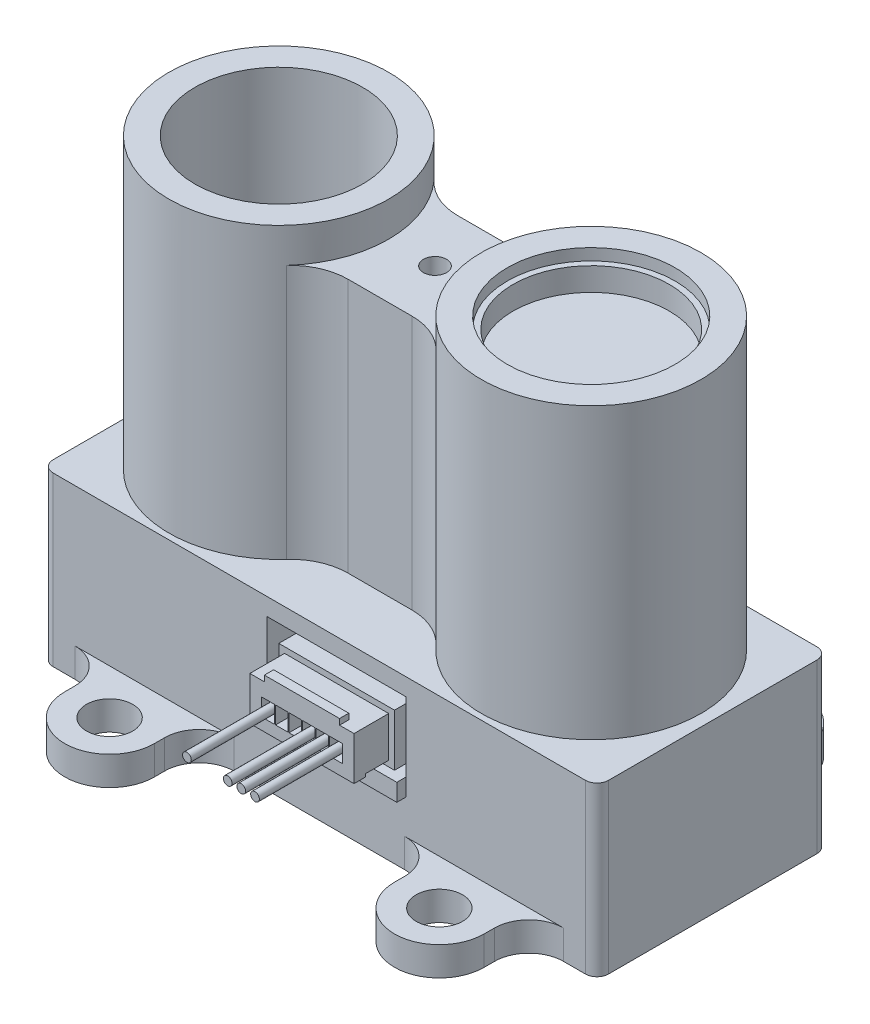
SolidWorks part; units mm, degrees
material "LiDar"
ref_plane "Front Plane" through (0, 0, 0) normal (0, 0, 1) x (1, 0, 0)
ref_plane "Top Plane" through (0, 0, 0) normal (0, 1, 0) x (1, 0, 0)
ref_plane "Right Plane" through (0, 0, 0) normal (1, 0, 0) x (0, 0, -1)
sketch "Sketch1" plane through (0, 0, 0) normal (0, 1, 0) x (1, 0, 0)
  line L1 (-24, 10) -> (24, 10)
  line L2 (-24, 10) -> (-24, -10)
  line L3 (-24, -10) -> (24, -10)
  line L4 (24, 10) -> (24, -10)
  point P4 (0, 10)
  point P6 (-24, 0)
  dimension "D1" = 20
  dimension "D2" = 48
extrude "Boss-Extrude1" add sketch "Sketch1" along normal blind 14.5
fillet "Fillet1" radius 1 4 edges at (-24, 7.25, -10) (-24, 7.25, 10) (24, 7.25, -10) (24, 7.25, 10)
sketch "Sketch2" plane through (0, 14.5, 0) normal (0, 1, 0) x (1, 0, 0)
  line L0 (-24, 9) -> (-24, -9) construction
  line L1 (0, -7.975) -> (0, 7.975) construction
  circle A0 centre (-13.5, 0) radius 9.5
  circle A1 centre (13.5, 0) radius 9.5
  point P2 (-23, 0)
  dimension "D1" = 19
  dimension "D2" = 1
extrude "Boss-Extrude2" add sketch "Sketch2" along normal blind 25
sketch "Sketch3" plane through (0, 14.5, 0) normal (0, 1, 0) x (1, 0, 0)
  line L1 (-5.2728, 4.75) -> (5.2728, 4.75)
  line L2 (-5.2728, 4.75) -> (-5.2728, -4.75)
  line L3 (-5.2728, -4.75) -> (5.2728, -4.75)
  line L4 (5.2728, 4.75) -> (5.2728, -4.75)
  circle A0 centre (-13.5, 0) radius 9.5 construction
  circle A1 centre (13.5, 0) radius 9.5 construction
  point P8 (-5.2728, 0)
  dimension "D1" = 9.5
extrude "Boss-Extrude3" add sketch "Sketch3" along normal blind 22
fillet "Fillet2" radius 5 4 edges at (5.2728, 25.5, -4.75) (-5.2728, 25.5, -4.75) (5.2728, 25.5, 4.75) (-5.2728, 25.5, 4.75)
sketch "Sketch4" plane through (0, 36.5, 0) normal (0, 1, 0) x (1, 0, 0)
  circle A0 centre (0, 0) radius 1
  dimension "D1" = 2
extrude "Cut-Extrude1" cut sketch "Sketch4" against normal blind 5
sketch "Sketch5" plane through (0, 39.5, 0) normal (0, 1, 0) x (1, 0, 0)
  circle A0 centre (-13.5, 0) radius 7.25
  circle A1 centre (-13.5, 0) radius 9.5 construction
  dimension "D1" = 14.5
extrude "Cut-Extrude2" cut sketch "Sketch5" against normal blind 13
sketch "Sketch6" plane through (0, 0, 0) normal (0, 0, 1) x (1, 0, 0)
  line L0 (-20.75, 39.5) -> (-20.75, 26.5) construction
  line L1 (-20.75, 28.5) -> (-20.25, 28.5)
  line L2 (-20.75, 28.5) -> (-20.75, 26.5)
  line L3 (-20.75, 26.5) -> (-20.25, 26.5)
  line L4 (-20.25, 28.5) -> (-20.25, 26.5)
  line L5 (-6.25, 26.5) -> (-20.75, 26.5) construction
  line L6 (-13.5, 39.5) -> (-13.5, 26.5) construction
  line L7 (-6.25, 39.5) -> (-20.75, 39.5) construction
  dimension "D1" = 2
  dimension "D2" = 0.5
revolve "Revolve1" add sketch "Sketch6" angle 360 about L6
sketch "Sketch7" plane through (0, 0, 0) normal (0, 0, 1) x (1, 0, 0)
  line L0 (-20.25, 26.5) -> (-13.5, 26.5)
  line L1 (-6.75, 26.5) -> (-20.25, 26.5) construction
  line L2 (-13.5, 26.5) -> (-13.5, 28.5)
  line L3 (-6.75, 28.5) -> (-20.25, 28.5) construction
  ellipse E0 centre (-13.5, 26.5) end of major axis (-20.25, 26.5) minor radius 2 (-20.25, 26.5) -> (-13.5, 28.5) cw
revolve "Revolve2" add sketch "Sketch7" angle 360 about L2
sketch "Sketch8" plane through (0, 39.5, 0) normal (0, 1, 0) x (1, 0, 0)
  circle A0 centre (13.5, 0) radius 7.25
  circle A1 centre (13.5, 0) radius 9.5 construction
  circle A2 centre (-13.5, 0) radius 7.25 construction
extrude "Cut-Extrude3" cut sketch "Sketch8" against normal blind 3
sketch "Sketch9" plane through (0, 0, 0) normal (0, 0, 1) x (1, 0, 0)
  line L0 (13.5, 36.5) -> (13.5, 39.5) construction
  line L1 (20.75, 36.5) -> (20.25, 36.5)
  line L2 (20.75, 36.5) -> (20.75, 38.5)
  line L3 (20.75, 38.5) -> (20.25, 38.5)
  line L4 (20.25, 36.5) -> (20.25, 38.5)
  line L5 (20.75, 36.5) -> (6.25, 36.5) construction
  line L6 (23, 39.5) -> (4, 39.5) construction
  dimension "D1" = 2
  dimension "D2" = 0.5
revolve "Revolve3" add sketch "Sketch9" angle 360 about L0
sketch "Sketch11" plane through (0, 0, 10) normal (0, 0, 1) x (1, 0, 0)
  line L0 (24, 14.5) -> (24, 0) construction
  line L1 (-3, 11) -> (6, 11)
  line L2 (-3, 11) -> (-3, 7.5)
  line L3 (-3, 7.5) -> (6, 7.5)
  line L4 (6, 11) -> (6, 7.5)
  line L5 (-23, 0) -> (23, 0) construction
  dimension "D1" = 18
  dimension "D2" = 9
  dimension "D3" = 3.5
  dimension "D4" = 11
extrude "Boss-Extrude4" add sketch "Sketch11" along normal blind 3
sketch "Sketch12" plane through (0, 0, 13) normal (0, 0, 1) x (1, 0, 0)
  line L0 (6, 11) -> (-3, 11) construction
  line L1 (-1.75, 11) -> (4.75, 11)
  line L2 (-1.75, 11) -> (-1.75, 11.5)
  line L3 (-1.75, 11.5) -> (4.75, 11.5)
  line L4 (4.75, 11) -> (4.75, 11.5)
  point P6 (1.5, 11)
  dimension "D1" = 6.5
  dimension "D2" = 0.5
extrude "Boss-Extrude5" add sketch "Sketch12" against normal blind 0.8
sketch "Sketch13" plane through (0, 0, 13) normal (0, 0, 1) x (1, 0, 0)
  line L1 (-3, 7.5) -> (6, 7.5)
  line L2 (-3, 7.5) -> (-3, 7.25)
  line L3 (-3, 7.25) -> (6, 7.25)
  line L4 (6, 7.5) -> (6, 7.25)
  dimension "D1" = 0.25
extrude "Boss-Extrude6" add sketch "Sketch13" against normal blind 1
sketch "Sketch14" plane through (0, 0, 10) normal (0, 0, 1) x (1, 0, 0)
  line L1 (-4.5, 7) -> (7.5, 7)
  line L2 (-4.5, 7) -> (-4.5, 5.5)
  line L3 (-4.5, 5.5) -> (7.5, 5.5)
  line L4 (7.5, 7) -> (7.5, 5.5)
  line L5 (-23, 0) -> (23, 0) construction
  line L6 (-3, 7.5) -> (6, 7.5) construction
  point P9 (1.5, 7.5)
  point P10 (1.5, 7)
  dimension "D1" = 1.5
  dimension "D2" = 12
  dimension "D3" = 5.5
extrude "Boss-Extrude7" add sketch "Sketch14" along normal blind 0.8
sketch "Sketch15" plane through (0, 0, 10) normal (0, 0, 1) x (1, 0, 0)
  line L0 (-4.5, 7) -> (-4.5, 13)
  line L1 (-4.5, 13) -> (7.5, 13)
  line L2 (7.5, 13) -> (7.5, 7)
  line L8 (-4.5, 5.5) -> (7.5, 5.5) construction
  line L10 (-4.5, 7) -> (-3.5, 7)
  line L11 (-3.5, 7) -> (-3.5, 11.5)
  line L12 (-3.5, 11.5) -> (6.5, 11.5)
  line L13 (6.5, 11.5) -> (6.5, 7)
  line L14 (7.5, 7) -> (-4.5, 7) construction
  line L15 (6.5, 7) -> (7.5, 7)
  dimension "D1" = 7.5
  dimension "D2" = 1.5
  dimension "D3" = 1
  dimension "D4" = 1
extrude "Cut-Extrude4" cut sketch "Sketch15" against normal blind 5
sketch "Sketch16" plane through (0, 0, 0) normal (0, -1, 0) x (1, 0, 0)
  line L0 (-23, 10) -> (23, 10) construction
  line L1 (-18.125, 10) -> (-10.375, 10)
  line L2 (-18.125, 10) -> (-18.125, 17.75)
  line L3 (-18.125, 17.75) -> (-10.375, 17.75)
  line L4 (-10.375, 10) -> (-10.375, 17.75)
  line L5 (-18.125, 17.75) -> (-10.375, 10) construction
  line L6 (-24, -9) -> (-24, 9) construction
  circle A0 centre (-14.25, 13.875) radius 2
  dimension "D4" = 4
  dimension "D1" = 7.75
  dimension "D2" = 7.75
  dimension "D3" = 45
  dimension "D5" = 9.75
extrude "Boss-Extrude8" add sketch "Sketch16" against normal blind 2.5
mirror "Mirror3" about plane through (0, 0, 0) normal (0, 0, 1) of "Boss-Extrude8"
mirror "Mirror4" about plane through (0, 0, 0) normal (1, 0, 0) of "Mirror3", "Boss-Extrude8"
fillet "Fillet3" 2 edges at (-18.125, 1.25, 17.75) (-10.375, 1.25, 17.75) type full round first side face at (-18.125, 1.25, 13.875) second side face at (-10.375, 1.25, 13.875) middle face at (-14.25, 1.25, 17.75)
fillet "Fillet5" 2 edges at (10.375, 1.25, 17.75) (18.125, 1.25, 17.75) type full round first side face at (10.375, 1.25, 13.875) second side face at (18.125, 1.25, 13.875) middle face at (14.25, 1.25, 17.75)
fillet "Fillet6" 2 edges at (-18.125, 1.25, -17.75) (-10.375, 1.25, -17.75) type full round first side face at (-18.125, 1.25, -13.875) second side face at (-10.375, 1.25, -13.875) middle face at (-14.25, 1.25, -17.75)
fillet "Fillet7" 2 edges at (10.375, 1.25, -17.75) (18.125, 1.25, -17.75) type full round first side face at (10.375, 1.25, -13.875) second side face at (18.125, 1.25, -13.875) middle face at (14.25, 1.25, -17.75)
fillet "Fillet4" radius 3 8 edges at (-10.375, 1.25, 10) (-18.125, 1.25, 10) (18.125, 1.25, -10) (10.375, 1.25, -10) (-10.375, 1.25, -10) (-18.125, 1.25, -10) (18.125, 1.25, 10) (10.375, 1.25, 10)
sketch "Sketch17" plane through (0, 0, 13) normal (0, 0, 1) x (1, 0, 0)
  line L0 (-3, 7.25) -> (6, 7.25) construction
  line L1 (-2, 9.75) -> (5, 9.75)
  line L2 (-2, 9.75) -> (-2, 8.25)
  line L3 (-2, 8.25) -> (5, 8.25)
  line L4 (5, 9.75) -> (5, 8.25)
  point P6 (1.5, 7.25)
  point P7 (1.5, 9.75)
  dimension "D1" = 7
  dimension "D2" = 1.5
  dimension "D3" = 1
extrude "Cut-Extrude5" cut sketch "Sketch17" against normal blind 3
sketch "Sketch18" plane through (0, 0, 10) normal (0, 0, 1) x (1, 0, 0)
  line L0 (5, 9.75) -> (-2, 9.75) construction
  line L1 (-0.7833, 9.75) -> (-0.8833, 9.75)
  line L2 (-0.7833, 9.75) -> (-0.7833, 8.25)
  line L3 (-0.7833, 8.25) -> (-0.8833, 8.25)
  line L4 (-0.8833, 9.75) -> (-0.8833, 8.25)
  line L5 (-2, 8.25) -> (5, 8.25) construction
  line L6 (-2, 9.75) -> (-0.8333, 9.75) construction
  line L7 (0.3833, 9.75) -> (0.2833, 9.75)
  line L8 (0.3833, 9.75) -> (0.3833, 8.25)
  line L9 (0.3833, 8.25) -> (0.2833, 8.25)
  line L10 (0.2833, 9.75) -> (0.2833, 8.25)
  line L11 (-0.8333, 9.75) -> (0.3333, 9.75) construction
  line L12 (1.55, 9.75) -> (1.45, 9.75)
  line L13 (1.55, 9.75) -> (1.55, 8.25)
  line L14 (1.55, 8.25) -> (1.45, 8.25)
  line L15 (1.45, 9.75) -> (1.45, 8.25)
  line L16 (0.3333, 9.75) -> (1.5, 9.75) construction
  line L17 (2.7167, 9.75) -> (2.6167, 9.75)
  line L18 (2.7167, 9.75) -> (2.7167, 8.25)
  line L19 (2.7167, 8.25) -> (2.6167, 8.25)
  line L20 (2.6167, 9.75) -> (2.6167, 8.25)
  line L21 (1.5, 9.75) -> (2.6667, 9.75) construction
  line L22 (3.8833, 9.75) -> (3.7833, 9.75)
  line L23 (3.8833, 9.75) -> (3.8833, 8.25)
  line L24 (3.8833, 8.25) -> (3.7833, 8.25)
  line L25 (3.7833, 9.75) -> (3.7833, 8.25)
  line L26 (2.6667, 9.75) -> (3.8333, 9.75) construction
  line L27 (3.8333, 9.75) -> (5, 9.75) construction
  line L28 (5, 8.25) -> (5, 9.75) construction
  line L29 (5, 8.25) -> (5, 9.75) construction
  dimension "D2" = 0.1
  dimension "D1" = 5
extrude "Boss-Extrude9" add sketch "Sketch18" along normal blind 3
sketch "Sketch19" plane through (0, 0, 10) normal (0, 0, 1) x (1, 0, 0)
  line L0 (3.8833, 9.75) -> (5, 8.25) construction
  line L1 (2.7167, 9.75) -> (3.7833, 8.25) construction
  line L2 (1.55, 9.75) -> (2.6167, 8.25) construction
  line L3 (-2, 9.75) -> (-0.8833, 8.25) construction
  circle A1 centre (-1.4417, 9) radius 0.375
  circle A2 centre (2.0833, 9) radius 0.375
  circle A3 centre (3.25, 9) radius 0.375
  circle A4 centre (4.4417, 9) radius 0.375
  dimension "D1" = 0.75
extrude "Boss-Extrude10" add sketch "Sketch19" along normal blind 10
